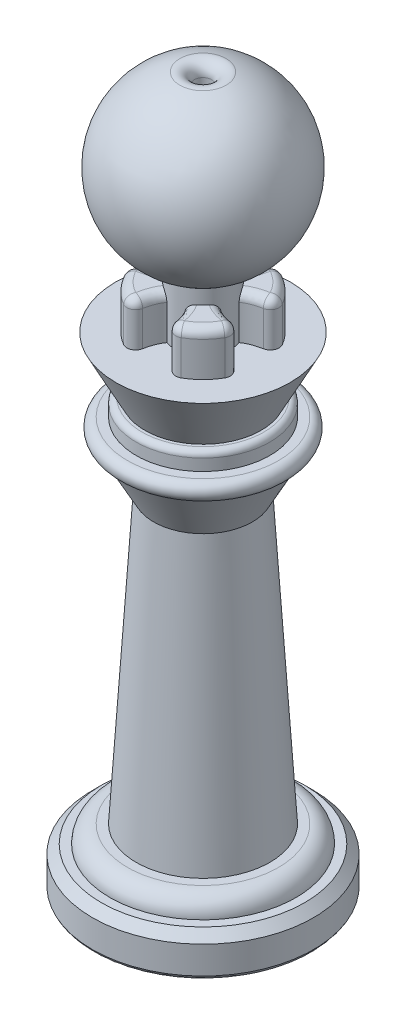
SolidWorks part; units mm, degrees
ref_plane "Front Plane" through (0, 0, 0) normal (0, 0, 1) x (1, 0, 0)
ref_plane "Top Plane" through (0, 0, 0) normal (0, 1, 0) x (1, 0, 0)
ref_plane "Right Plane" through (0, 0, 0) normal (1, 0, 0) x (0, 0, -1)
sketch "Sketch1" plane through (0, 0, 0) normal (0, 0, 1) x (1, 0, 0)
  line L0 (0, 0) -> (0, 45.72) construction
  line L1 (0, 0) -> (-9.652, 0)
  line L3 (-8.128, 3.175) -> (-9.652, 3.175)
  line L4 (-9.652, 0) -> (-9.652, 3.175)
  line L7 (-5.842, 4.699) -> (-8.128, 4.699)
  line L8 (-8.128, 3.175) -> (-8.128, 4.699)
  line L9 (-5.842, 4.699) -> (-4.318, 29.7074)
  line L10 (-4.318, 29.7074) -> (-6.604, 33.9683)
  line L11 (-6.604, 35.4923) -> (-5.842, 35.4923)
  line L16 (-5.842, 35.4923) -> (-5.842, 37.0163)
  line L17 (-5.842, 37.0163) -> (-5.08, 37.0163)
  line L18 (-5.08, 37.0163) -> (-7.62, 41.91)
  line L19 (0, 0) -> (0, 45.72)
  line L20 (0, 45.72) -> (-5.08, 45.72)
  line L21 (-5.08, 45.72) -> (-5.08, 41.91)
  line L22 (-5.08, 41.91) -> (-7.62, 41.91)
  arc A1 (-6.604, 35.4923) -> (-6.604, 33.9683) centre (-6.604, 34.7303) ccw
  point P25 (-7.0701, 36.3947)
  dimension "D10" = 1.524
  dimension "D1" = 9.652
  dimension "D2" = 3.175
  dimension "D3" = 1.524
  dimension "D4" = 1.524
  dimension "D5" = 3.81
  dimension "D6" = 2.286
  dimension "D7" = 4.318
  dimension "D8" = 6.604
  dimension "D9" = 1.524
  dimension "D11" = 1.524
  dimension "D12" = 0.762
  dimension "D13" = 5.08
  dimension "D14" = 7.62
  dimension "D15" = 5.08
  dimension "D16" = 45.72
revolve "Revolve1" add sketch "Sketch1" angle 360 about L0
fillet "Fillet2" radius 1.524 1 edges at (0, 4.699, -8.128)
chamfer "Chamfer1" distance 0.762 angle 45 1 edges at (0, 3.175, -9.652)
fillet "Fillet3" radius 0.508 1 edges at (0, 37.0163, -5.842)
sketch "Sketch2" plane through (0, 45.72, 0) normal (0, 1, 0) x (1, 0, 0)
  circle A0 centre (0, 0) radius 5.08 construction
  circle A1 centre (0, 0) radius 5.08 construction
  ellipse E0 centre (0, 5.08) end of major axis (0, 8.2647) minor radius 1.4951
  ellipse E1 centre (5.08, 0) end of major axis (1.8953, 0) minor radius 1.4951
  ellipse E2 centre (0, -5.08) end of major axis (0, -8.2647) minor radius 1.4951
  ellipse E3 centre (-5.08, 0) end of major axis (-8.2647, 0) minor radius 1.4951
  point P31 (0, 0)
  dimension "D1" = 4
extrude "Cut-Extrude1" cut sketch "Sketch2" against normal up to surface (3.81 mm away) up to face at (0, 41.91, -7.62)
fillet "Fillet4" radius 0.762 16 edges at (1.8953, 45.72, 0) (3.5921, 45.72, 3.5921) (0, 45.72, 1.8953) (-3.5921, 45.72, 3.5921) (-1.8953, 45.72, 0) (-3.5921, 45.72, -3.5921) (0, 45.72, -1.8953) (3.5921, 45.72, -3.5921) (-4.8561, 43.815, -1.4914) (-4.8561, 43.815, 1.4914) (-1.4914, 43.815, 4.8561) (4.8561, 43.815, 1.4914) (4.8561, 43.815, -1.4914) (1.4914, 43.815, -4.8561) (-1.4914, 43.815, -4.8561) (1.4914, 43.815, 4.8561)
sketch "Sketch4" plane through (0, 0, 0) normal (0, -1, 0) x (1, 0, 0)
  circle A0 centre (0, 0) radius 9.652 construction
  point P0 (0, 0)
  point P3 (9.6443, 0.3852)
sketch "Sketch5" plane through (0, 45.72, 0) normal (0, 1, 0) x (1, 0, 0)
  point P0 (0, 0)
ref_plane "Plane1" through (0, 0, 0) normal (-0.0399, 0, 0.9992) x (0.9992, 0, 0.0399)
sketch "Sketch6" plane through (0, 0, 0) normal (-0.0399, 0, 0.9992) x (0.9992, 0, 0.0399)
  line L0 (-2.5, 47.32) -> (-2.5, 41.91)
  line L3 (0, 41.91) -> (0, 47.32)
  line L4 (-10, 0) -> (0, 0)
  line L5 (-10, 0) -> (-5.37, -2.68)
  line L6 (-5.37, -2.68) -> (0, -2.68)
  line L7 (0, -2.68) -> (0, 0)
  line L8 (7.62, 41.91) -> (-7.62, 41.91) construction
  line L9 (0, 47.32) -> (-2.5, 47.32)
  line L10 (-2.5, 41.91) -> (0, 41.91)
  line L11 (0, 47.32) -> (0, 64.0197) construction
  circle A0 centre (0, 54.3911) radius 7.5
  dimension "D8" = 15
  dimension "D2" = 2.68
  dimension "D3" = 5.37
  dimension "D4" = 10
  dimension "D5" = 2.5
  dimension "D6" = 50
  dimension "D7" = 2.5
revolve "Revolve2" add sketch "Sketch6" angle 360 about L11 region at (-1.2663, 44.4728, -0.0506) region at (-3.1989, 54.4505, -0.1278) region at (-0.9404, 47.148, -0.0376) region at (-3.9556, -1.2054, -0.158)
sketch "Sketch7" plane through (0, -2.68, 0) normal (0, -1, 0) x (1, 0, 0)
  circle A0 centre (0, 0) radius 0.75
  dimension "D1" = 1.5
extrude "Cut-Extrude2" cut sketch "Sketch7" against normal blind 65
sketch "Sketch8" plane through (0, -2.68, 0) normal (0, -1, 0) x (1, 0, 0)
  circle A0 centre (0, 0) radius 5.1
  dimension "D1" = 10.2
extrude "Cut-Extrude3" cut sketch "Sketch8" against normal blind 4 contours A0
fillet "Fillet6" radius 1 3 edges at (0, 0, -10) (0, 61.8535, -0.75) (0, -2.68, -5.1)
